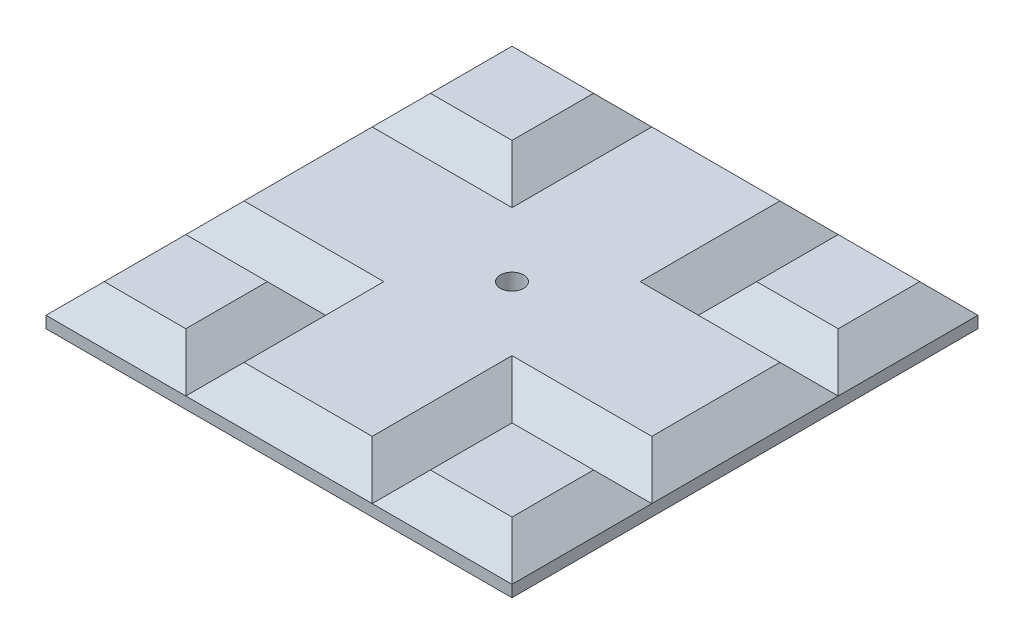
SolidWorks part; units mm, degrees
ref_plane "Front Plane" through (0, 0, 0) normal (0, 0, 1) x (1, 0, 0)
ref_plane "Top Plane" through (0, 0, 0) normal (0, 1, 0) x (1, 0, 0)
ref_plane "Right Plane" through (0, 0, 0) normal (1, 0, 0) x (0, 0, -1)
sketch "Sketch1" plane through (0, 0, 0) normal (0, 1, 0) x (1, 0, 0)
  line L1 (-20, -20) -> (20, -20)
  line L2 (-20, -20) -> (-20, 20)
  line L3 (-20, 20) -> (20, 20)
  line L4 (20, -20) -> (20, 20)
  line L5 (-20, -20) -> (20, 20) construction
  line L6 (-20, 20) -> (20, -20) construction
  point P0 (0, 0)
  dimension "D1" = 40
  dimension "D2" = 40
extrude "Boss-Extrude1" add sketch "Sketch1" along normal blind 6
sketch "Sketch2" plane through (0, 0, 0) normal (0, -1, 0) x (1, 0, 0)
  line L0 (20, 20) -> (8, 20)
  line L1 (-20, 20) -> (-8, 20)
  line L2 (-20, 20) -> (-20, 8)
  line L3 (-20, 8) -> (-8, 8)
  line L4 (-8, 20) -> (-8, 8)
  line L5 (20, 20) -> (20, 8)
  line L6 (20, 8) -> (8, 8)
  line L7 (8, 20) -> (8, 8)
  line L8 (20, -20) -> (20, -8)
  line L9 (20, -20) -> (8, -20)
  line L10 (8, -20) -> (8, -8)
  line L11 (20, -8) -> (8, -8)
  line L12 (-20, -20) -> (-8, -20)
  line L13 (-20, -20) -> (-20, -8)
  line L14 (-20, -8) -> (-8, -8)
  line L15 (-8, -20) -> (-8, -8)
  point P20 (0, 0)
  dimension "D1" = 12
  dimension "D2" = 4
extrude "Cut-Extrude1" cut sketch "Sketch2" against normal blind 2.5
sketch "Sketch3" plane through (0, 6, 0) normal (0, 1, 0) x (1, 0, 0)
  line L0 (20, 20) -> (8, 20)
  line L1 (-20, 20) -> (-8, 20)
  line L2 (-20, 20) -> (-20, 8)
  line L3 (-20, 8) -> (-8, 8)
  line L4 (-8, 20) -> (-8, 8)
  line L5 (20, 20) -> (20, 8)
  line L6 (20, 8) -> (8, 8)
  line L7 (8, 20) -> (8, 8)
  line L8 (20, -20) -> (20, -8)
  line L9 (20, -20) -> (8, -20)
  line L10 (8, -20) -> (8, -8)
  line L11 (20, -8) -> (8, -8)
  line L12 (-20, -20) -> (-8, -20)
  line L13 (-20, -20) -> (-20, -8)
  line L14 (-20, -8) -> (-8, -8)
  line L15 (-8, -20) -> (-8, -8)
  point P20 (0, 0)
  dimension "D1" = 12
  dimension "D2" = 4
extrude "Cut-Extrude2" cut sketch "Sketch3" against normal blind 2.5
chamfer "Chamfer1" distance 2.5 angle 45 24 edges at (-14, 6, -8) (-8, 6, -14) (0, 6, -20) (8, 6, -14) (14, 6, -8) (20, 6, 0) (14, 6, 8) (8, 6, 14) (0, 6, 20) (-8, 6, 14) (-14, 6, 8) (-20, 6, 0) (-20, 0, 0) (-14, 0, 8) (-8, 0, 14) (0, 0, 20) (8, 0, 14) (14, 0, 8) (20, 0, 0) (14, 0, -8) (8, 0, -14) (0, 0, -20) (-8, 0, -14) (-14, 0, -8)
sketch "Sketch4" plane through (0, 2.5, 0) normal (0, -1, 0) x (1, 0, 0)
  line L0 (8, -8) -> (20, -8)
  line L1 (8, 8) -> (20, 8)
  line L2 (8, 8) -> (8, 20)
  line L3 (8, 20) -> (20, 20)
  line L4 (20, 8) -> (20, 20)
  line L5 (8, -8) -> (8, -20)
  line L6 (8, -20) -> (20, -20)
  line L7 (20, -8) -> (20, -20)
  line L8 (-8, -8) -> (-8, -20)
  line L9 (-8, -8) -> (-20, -8)
  line L10 (-20, -8) -> (-20, -20)
  line L11 (-8, -20) -> (-20, -20)
  line L12 (-8, 8) -> (-20, 8)
  line L13 (-8, 8) -> (-8, 20)
  line L14 (-8, 20) -> (-20, 20)
  line L15 (-20, 8) -> (-20, 20)
  point P21 (0, 0)
  dimension "D1" = 4
extrude "Boss-Extrude2" add sketch "Sketch4" along normal blind 2.5
sketch "Sketch5" plane through (0, 3.5, 0) normal (0, 1, 0) x (1, 0, 0)
  line L0 (-8, -8) -> (-20, -8)
  line L1 (8, -8) -> (20, -8)
  line L2 (8, -8) -> (8, -20)
  line L3 (8, -20) -> (20, -20)
  line L4 (20, -8) -> (20, -20)
  line L5 (-8, -8) -> (-8, -20)
  line L6 (-8, -20) -> (-20, -20)
  line L7 (-20, -8) -> (-20, -20)
  line L8 (-8, 8) -> (-8, 20)
  line L9 (-8, 8) -> (-20, 8)
  line L10 (-20, 8) -> (-20, 20)
  line L11 (-8, 20) -> (-20, 20)
  line L12 (8, 8) -> (20, 8)
  line L13 (8, 8) -> (8, 20)
  line L14 (8, 20) -> (20, 20)
  line L15 (20, 8) -> (20, 20)
  point P20 (0, 0)
  dimension "D1" = 4
extrude "Boss-Extrude3" add sketch "Sketch5" along normal blind 2.5
chamfer "Chamfer2" distance 2.5 angle 45 32 edges at (14, 6, 8) (20, 6, 14) (14, 6, 20) (8, 6, 14) (-8, 0, -14) (-14, 0, -20) (-20, 0, -14) (-14, 0, -8) (-14, 0, 8) (-20, 0, 14) (-14, 0, 20) (-8, 0, 14) (14, 0, 20) (20, 0, 14) (14, 0, 8) (8, 0, 14) (14, 0, -8) (20, 0, -14) (14, 0, -20) (8, 0, -14) (14, 6, -20) (20, 6, -14) (14, 6, -8) (8, 6, -14) (-20, 6, -14) (-14, 6, -20) (-8, 6, -14) (-14, 6, -8) (-14, 6, 20) (-20, 6, 14) (-14, 6, 8) (-8, 6, 14)
sketch "Sketch6" plane through (0, 0, 0) normal (0, -1, 0) x (1, 0, 0)
  line L0 (10.5, 10.5) -> (17.5, 17.5) construction
  line L1 (17.5, 17.5) -> (10.5, 17.5) construction
  line L2 (10.5, 17.5) -> (17.5, 10.5) construction
  circle A0 centre (14, 14) radius 2.5
  circle A1 centre (14, -14) radius 2.5
  circle A2 centre (-14, -14) radius 2.5
  circle A3 centre (-14, 14) radius 2.5
  point P19 (0, 0)
  dimension "D1" = 4
extrude "Cut-Extrude3" cut sketch "Sketch6" against normal blind 2.5
sketch "Sketch7" plane through (0, 6, 0) normal (0, 1, 0) x (1, 0, 0)
  circle A0 centre (0, 0) radius 1
extrude "Cut-Extrude4" cut sketch "Sketch7" against normal through all
